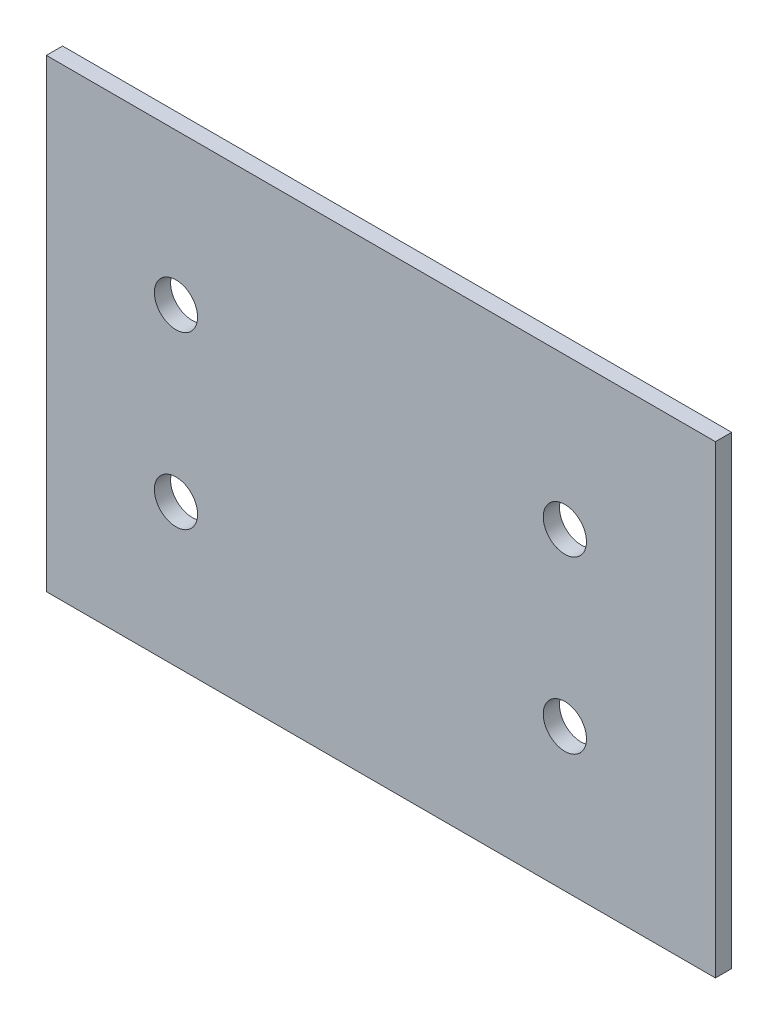
SolidWorks part; units mm, degrees
ref_plane "Front Plane" through (0, 0, 0) normal (0, 0, 1) x (1, 0, 0)
ref_plane "Top Plane" through (0, 0, 0) normal (0, 1, 0) x (1, 0, 0)
ref_plane "Right Plane" through (0, 0, 0) normal (1, 0, 0) x (0, 0, -1)
sketch "Sketch1" plane through (0, 0, 0) normal (0, 0, 1) x (1, 0, 0)
  line L1 (-39.3319, 27.305) -> (39.3319, 27.305)
  line L2 (-39.3319, 27.305) -> (-39.3319, -27.305)
  line L3 (-39.3319, -27.305) -> (39.3319, -27.305)
  line L4 (39.3319, 27.305) -> (39.3319, -27.305)
  line L5 (-39.3319, 27.305) -> (39.3319, -27.305) construction
  line L6 (-39.3319, -27.305) -> (39.3319, 27.305) construction
  point P0 (0, 0)
  dimension "D13" = 78.6638
  dimension "D2" = 54.61
extrude "Boss-Extrude1" add sketch "Sketch1" along normal blind 1.905
sketch "Sketch2" plane through (0, 0, 1.905) normal (0, 0, 1) x (1, 0, 0)
  line L0 (39.3319, 27.305) -> (-39.3319, 27.305) construction
  line L1 (-39.3319, 27.305) -> (-39.3319, -27.305) construction
  circle A0 centre (-24.0919, 9.525) radius 2.54
  circle A1 centre (-24.0919, -10.541) radius 2.54
  circle A2 centre (21.6281, 9.525) radius 2.54
  circle A3 centre (21.6281, -10.541) radius 2.54
  dimension "D1" = 5.08
  dimension "D2" = 20.066
  dimension "D3" = 17.78
  dimension "D4" = 15.24
  dimension "D5" = 45.72
extrude "Cut-Extrude1" cut sketch "Sketch2" against normal through all
